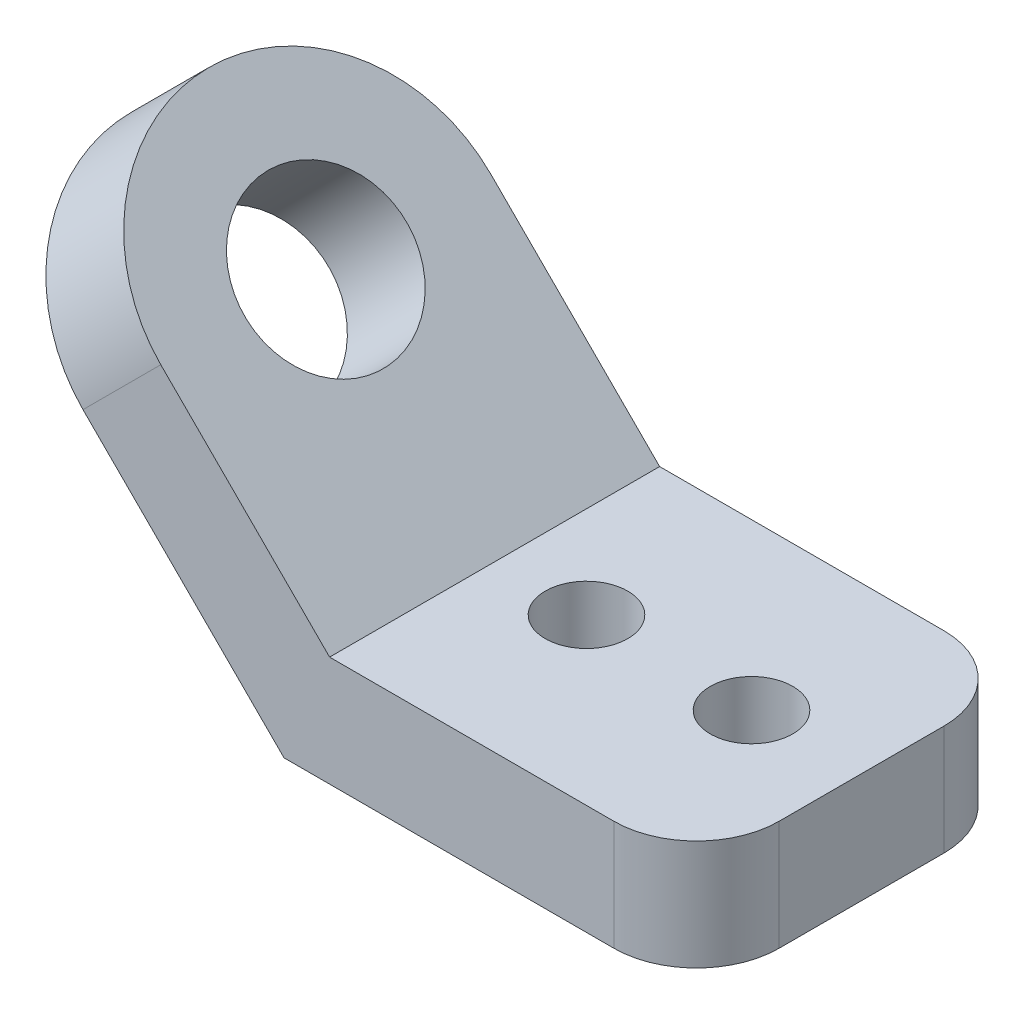
SolidWorks part; units mm, degrees
ref_plane "Alzado" through (0, 0, 0) normal (0, 0, 1) x (1, 0, 0)
ref_plane "Planta" through (0, 0, 0) normal (0, 1, 0) x (1, 0, 0)
ref_plane "Vista lateral" through (0, 0, 0) normal (1, 0, 0) x (0, 0, -1)
sketch "Croquis1" plane through (0, 0, 0) normal (0, 0, 1) x (1, 0, 0)
  line L0 (0, 0) -> (-7.4984, 0)
  line L1 (-7.4984, 0) -> (-13.2744, 5.776)
  line L2 (0, 2) -> (-6.67, 2)
  line L3 (-6.67, 2) -> (-11.8602, 7.1902)
  line L4 (-11.8602, 7.1902) -> (-13.2744, 5.776)
  line L5 (0, 2) -> (0, 0)
  dimension "D1" = 2
  dimension "D2" = 7.34
  dimension "D3" = 6.67
  dimension "D4" = 135
extrude "Saliente-Extruir1" add sketch "Croquis1" along normal mid plane 6
fillet "Redondeo1" radius 3 2 edges at (-12.5673, 6.4831, -3) (-12.5673, 6.4831, 3)
fillet "Redondeo2" radius 1.5 2 edges at (0, 1, -3) (0, 1, 3)
sketch "Croquis3" plane through (-2.335, -2.335, 0) normal (0.7071, 0.7071, 0) x (0, 0, -1)
  circle A0 centre (0, 10.4706) radius 1.475
  dimension "D1" = 2.95
extrude "Cortar-Extruir1" cut sketch "Croquis3" against normal through all
sketch "Croquis4" plane through (0, 2, 0) normal (0, 1, 0) x (1, 0, 0)
  circle A0 centre (-5, 0) radius 0.75
  circle A1 centre (-2, 0) radius 0.75
  dimension "D1" = 1.5
  dimension "D2" = 3
  dimension "D3" = 2
extrude "Cortar-Extruir2" cut sketch "Croquis4" against normal through all
